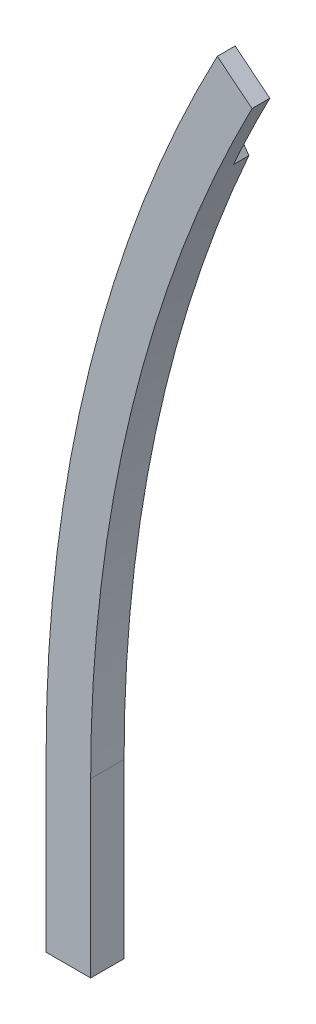
SolidWorks part; units mm, degrees
ref_plane "Front Plane" through (0, 0, 0) normal (0, 0, 1) x (1, 0, 0)
ref_plane "Top Plane" through (0, 0, 0) normal (0, 1, 0) x (1, 0, 0)
ref_plane "Right Plane" through (0, 0, 0) normal (1, 0, 0) x (0, 0, -1)
sketch "Sketch1" plane through (0, 0, 0) normal (0, 0, 1) x (1, 0, 0)
  line L0 (0, 0) -> (-12.7, 0)
  line L1 (-12.7, 0) -> (-12.7, 49.2125)
  line L4 (77.0255, 212.8537) -> (23.6406, 255.6026) construction
  line L5 (-12.7, 47.244) -> (-12.7, -82.4033) construction
  line L6 (0, 0) -> (0, 49.2125)
  line L8 (46.0126, 237.6879) -> (36.0992, 245.6261)
  line L9 (-16.256, 49.2125) -> (-42.799, 49.2125) construction
  arc A1 (36.0992, 245.6261) -> (-12.7, 49.2125) centre (406.9754, 49.2125) ccw
  arc A2 (46.0126, 237.6879) -> (0, 49.2125) centre (409.0201, 49.2125) ccw
  dimension "D1" = 419.6754
extrude "Boss-Extrude1" add sketch "Sketch1" along normal blind 9.525
sketch "Sketch3" plane through (0, 0, 0) normal (0, 0, -1) x (-1, 0, 0)
  line L15 (-27.3494, 228.1303) -> (-35.5812, 216.0682)
  line L16 (-14.4265, 247.0664) -> (-68.4749, 167.8686) construction
  line L19 (0, 49.2125) -> (0, 0)
  line L20 (0, 0) -> (12.7, 0)
  line L21 (12.7, 0) -> (12.7, 49.2125)
  line L22 (-36.0992, 245.6261) -> (-46.0126, 237.6879)
  line L26 (-36.0992, 245.6261) -> (-46.0126, 237.6879)
  arc A10 (12.7, 49.2125) -> (-36.0992, 245.6261) centre (-406.9754, 49.2125) ccw
  arc A11 (0, 49.2125) -> (-46.0126, 237.6879) centre (-409.0201, 49.2125) ccw
  arc A12 (-27.3494, 228.1303) -> (-36.0992, 245.6261) centre (-406.9754, 49.2125) ccw
  arc A13 (-35.5812, 216.0682) -> (-46.0126, 237.6879) centre (-409.0201, 49.2125) ccw
  dimension "D1" = 0
extrude "Cut-Extrude5" cut sketch "Sketch3" against normal blind 4.445
